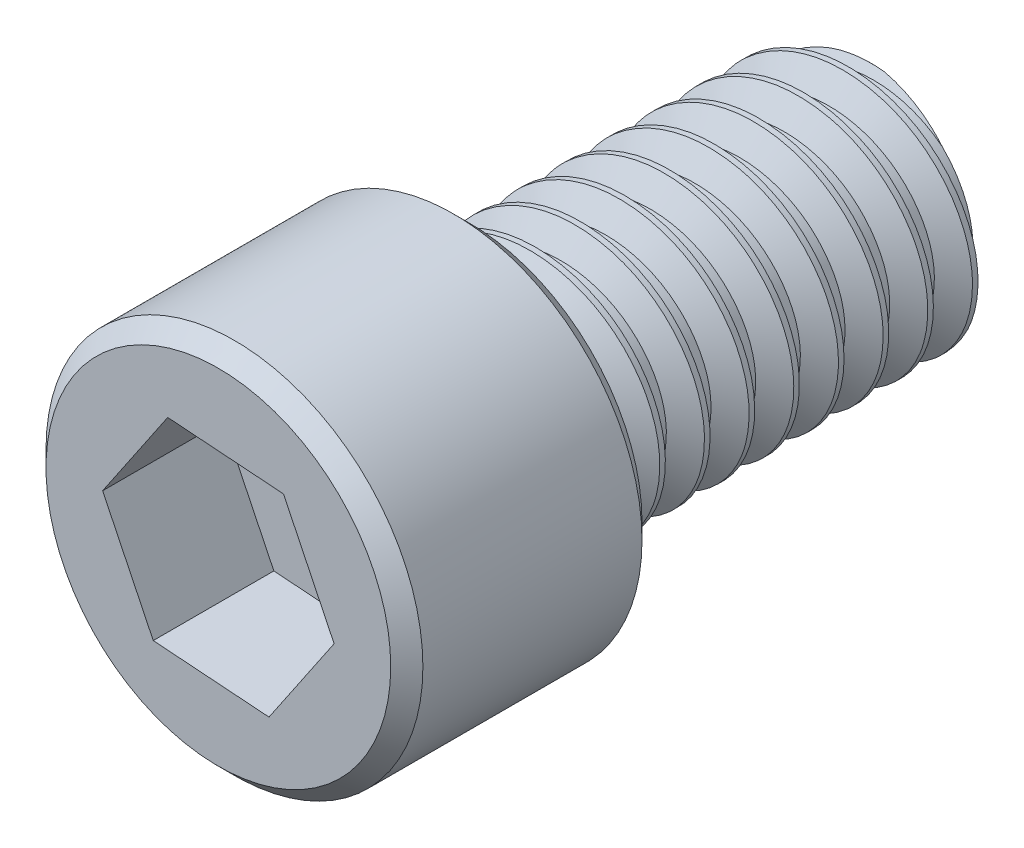
SolidWorks part; units mm, degrees
ref_plane "Front Plane" through (0, 0, 0) normal (0, 0, 1) x (1, 0, 0)
ref_plane "Top Plane" through (0, 0, 0) normal (0, 1, 0) x (1, 0, 0)
ref_plane "Right Plane" through (0, 0, 0) normal (1, 0, 0) x (0, 0, -1)
sketch "Sketch1" plane through (0, 0, 0) normal (0, 0, 1) x (1, 0, 0)
  circle A0 centre (0, 0) radius 5.9531
  dimension "D1" = 11.9062
extrude "Boss-Extrude1" add sketch "Sketch1" along normal blind 7.9375
sketch "Sketch3" plane through (0, 0, 0) normal (0, 0, -1) x (-1, 0, 0)
  circle A0 centre (0, 0) radius 3.9688
  dimension "D1" = 7.9375
extrude "Boss-Extrude2" add sketch "Sketch3" along normal blind 12.7
chamfer "Chamfer1" distance 0.508 angle 45 3 edges at (-3.9688, 0, -12.7) (5.9531, 0, 0) (5.9531, 0, 7.9375)
thread "Thread1" pitch 1.4111 start angle 0, offset 2.54, length 0, pitch 1.4111, diameter 7.9375
ref_plane "Plane1" through (3.9688, 0, -14.732) normal (0, -1, 0) x (1, 0, 0)
sketch "Thread Profile1" plane through (3.9688, 0, -14.732) normal (0, -1, 0) x (1, 0, 0)
  line L0 (0, 0) -> (0, 1.4111) construction
  line L11 (0, 0) -> (0, 1.2347)
  line L12 (0, 1.2347) -> (-0.7638, 0.7937)
  line L13 (-0.7638, 0.7937) -> (-0.7638, 0.441)
  line L15 (-0.7638, 0.441) -> (0, 0)
  line L17 (-0.7638, 0.6174) -> (0, 0.6174) construction
  point P2 (0, 0)
  dimension "Pitch" = 1.4111
  dimension "Profile_Angle" = 60
  dimension "Profile_Land" = 0.3528
  dimension "Profile_Height" = 0.7638
sketch "Sketch4" plane through (0, 0, 7.9375) normal (0, 0, 1) x (1, 0, 0)
  line L0 (0, 0) -> (5.4451, 0) construction
  line L2 (-2.0572, -3.0346) -> (1.5994, -3.2989)
  line L3 (1.5994, -3.2989) -> (3.6566, -0.2643)
  line L4 (3.6566, -0.2643) -> (2.0572, 3.0346)
  line L5 (2.0572, 3.0346) -> (-1.5994, 3.2989)
  line L6 (-1.5994, 3.2989) -> (-3.6566, 0.2643)
  line L7 (-3.6566, 0.2643) -> (-2.0572, -3.0346)
  circle A0 centre (0, 0) radius 5.4451 construction
  circle A1 centre (0, 0) radius 3.175 construction
  dimension "D1" = 6.35
extrude "Cut-Extrude1" cut sketch "Sketch4" against normal blind 3.81
